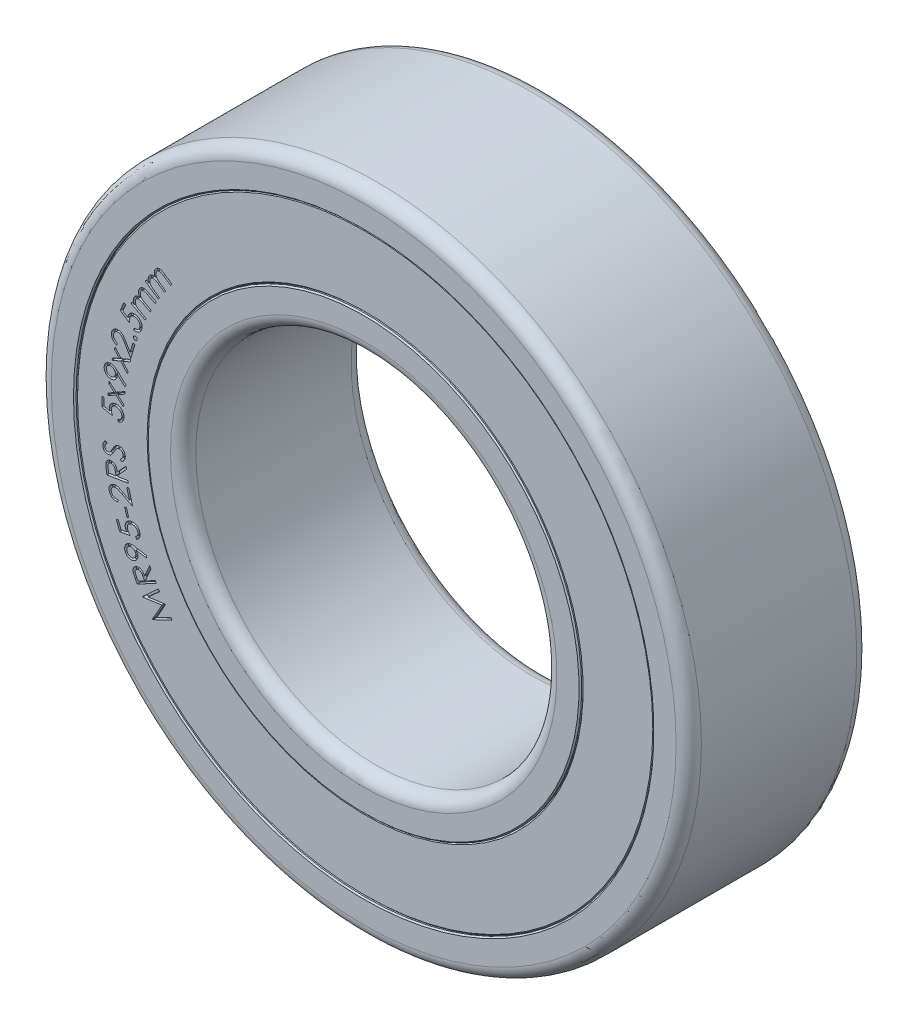
SolidWorks part; units mm, degrees
material "AISI 316 Annealed Stainless Steel Bar (SS)"
ref_plane "Front" through (0, 0, 0) normal (0, 0, 1) x (1, 0, 0)
ref_plane "Top" through (0, 0, 0) normal (0, 1, 0) x (1, 0, 0)
ref_plane "Right" through (0, 0, 0) normal (1, 0, 0) x (0, 0, -1)
sketch "LAYOUT R" plane through (0, 0, 0) normal (1, 0, 0) x (0, 0, -1)
  line L0 (-1.25, 2.5) -> (1.25, 2.5)
  line L1 (1.25, -4.5) -> (-1.25, -4.5) construction
  line L2 (1.25, -4.5) -> (1.25, 4.5) construction
  line L3 (1.25, 4.5) -> (-1.25, 4.5)
  line L4 (-1.25, -4.5) -> (-1.25, 4.5) construction
  line L5 (1.25, -4.5) -> (-1.25, 4.5) construction
  line L6 (1.25, 4.5) -> (-1.25, -4.5) construction
  line L7 (-1.25, 3) -> (1.25, 3)
  line L8 (-1.25, 4) -> (1.25, 4)
  line L11 (-17.5, 0) -> (17.5, 0) construction
  line L12 (-1.25, 4.5) -> (-1.25, 4)
  line L13 (1.25, 4.5) -> (1.25, 4)
  line L14 (-1.25, 4) -> (-1.25, 3)
  line L15 (1.25, 4) -> (1.25, 3)
  line L16 (-1.25, 3) -> (-1.25, 2.5)
  line L17 (1.25, 3) -> (1.25, 2.5)
  line L18 (-1.23, 4) -> (-1.23, 3)
  line L19 (1.23, 4) -> (1.23, 3)
  point P0 (0, 0)
  point P15 (0, 0)
  dimension "D1" = 2.5
  dimension "D2" = 9
  dimension "D3" = 2.5
  dimension "D6" = 0.02
  dimension "D7" = 0.02
  dimension "D4" = 3
  dimension "D5" = 4
sketch "Sketch R, INNER BODY" plane through (0, 0, 0) normal (1, 0, 0) x (0, 0, -1)
  line L0 (-1.25, 2.5) -> (1.25, 2.5) construction
  line L2 (-1.25, 3) -> (1.25, 3) construction
  line L4 (-1.25, 2.5) -> (1.25, 2.5)
  line L6 (-1.25, 3) -> (1.25, 3)
  line L8 (1.25, 3) -> (1.25, 2.5) construction
  line L9 (-1.25, 3) -> (-1.25, 2.5) construction
  line L10 (1.25, 3) -> (1.25, 2.5)
  line L11 (-1.25, 3) -> (-1.25, 2.5)
  line L12 (-17.5, 0) -> (17.5, 0) construction
  line L13 (-17.5, 0) -> (17.5, 0) construction
sketch "Sketch R, OUTER BODY" plane through (0, 0, 0) normal (1, 0, 0) x (0, 0, -1)
  line L2 (-1.25, 4) -> (1.25, 4) construction
  line L3 (1.25, 4.5) -> (-1.25, 4.5) construction
  line L6 (-1.25, 4) -> (1.25, 4)
  line L7 (1.25, 4.5) -> (-1.25, 4.5)
  line L8 (-17.5, 0) -> (17.5, 0) construction
  line L9 (-17.5, 0) -> (17.5, 0) construction
  line L10 (1.25, 4.5) -> (1.25, 4) construction
  line L11 (-1.25, 4.5) -> (-1.25, 4) construction
  line L12 (1.25, 4.5) -> (1.25, 4)
  line L13 (-1.25, 4.5) -> (-1.25, 4)
sketch "Sketch R, SEAL FACES" plane through (0, 0, 0) normal (1, 0, 0) x (0, 0, -1)
  line L0 (-17.5, 0) -> (17.5, 0) construction
  line L1 (-17.5, 0) -> (17.5, 0) construction
  line L3 (-1.25, 3) -> (1.25, 3) construction
  line L5 (-1.25, 4) -> (1.25, 4) construction
  line L7 (-1.23, 3) -> (1.23, 3)
  line L9 (-1.23, 4) -> (1.23, 4)
  line L10 (1.23, 4) -> (1.23, 3) construction
  line L11 (-1.23, 4) -> (-1.23, 3) construction
  line L12 (1.23, 4) -> (1.23, 3)
  line L13 (-1.23, 4) -> (-1.23, 3)
revolve "Revolve INNER BODY" add sketch "Sketch R, INNER BODY" angle 360 about L13
fillet "Fillet INNER BODY" radius 0.175 2 edges at (2.5, 0, 1.25) (2.5, 0, -1.25)
chamfer "Chamfer INNER BODY" distance 0.018 angle 45 2 edges at (3, 0, -1.25) (3, 0, 1.25)
revolve "Revolve OUTER BODY" add sketch "Sketch R, OUTER BODY" angle 360 about L9
fillet "Fillet OUTER BODY" radius 0.175 2 edges at (4.5, 0, -1.25) (4.5, 0, 1.25)
chamfer "Chamfer OUTER BODY" distance 0.018 angle 45 2 edges at (4, 0, 1.25) (4, 0, -1.25)
revolve "Revolve SEALS" add sketch "Sketch R, SEAL FACES" angle 360 about L1
chamfer "Chamfer SEALS" distance 0.018 angle 45 4 edges at (3, 0, -1.23) (4, 0, -1.23) (4, 0, 1.23) (3, 0, 1.23)
sketch "Sketch TEXT RADIUS 1 — MANUALLY ASSIGN TEXT AND FONT SIZE (FROM EQUATIONS)" plane through (0, 0, 1.23) normal (0, 0, 1) x (1, 0, 0)
  circle A0 centre (0, 0) radius 3.35 construction
  text T0 "MR95-2RS  5x9x2.5mm\r\n" font "Century Gothic" height 0.3
  dimension "D1" = 6.7
extrude "Cut-Extrude SEAL LABEL 1" cut sketch "Sketch TEXT RADIUS 1 — MANUALLY ASSIGN TEXT AND FONT SIZE (FROM EQUATIONS)" against normal blind 0.05
sketch "Sketch TEXT RADIUS 2 — MANUALLY ASSIGN TEXT AND FONT SIZE (FROM EQUATIONS)" plane through (0, 0, -1.23) normal (0, 0, -1) x (-1, 0, 0)
  circle A0 centre (0, 0) radius 3.35 construction
  text T0 "MR95-2RS  5x9x2.5mm" font "Century Gothic" height 0.3
  dimension "D1" = 6.7
extrude "Cut-Extrude SEAL LABEL 2" cut sketch "Sketch TEXT RADIUS 2 — MANUALLY ASSIGN TEXT AND FONT SIZE (FROM EQUATIONS)" against normal blind 0.05
equation "\"_i__BORE\"= 5"
equation "\"_i__OUTSIDE_DIAMETER\"= 9"
equation "\"_i__WIDTH\"= 2.5"
equation "\"_i_optional__TEXT_RADIUS_ADJUSTMENT\"= 0"
equation "\"_output__FONT_SIZE_mm\"= \"BODY_SPAN__SEAL__OF_RADIUS\" * \"param__FONT_SIZE_RATIO\"'MANUALLY ASSIGN TO FONT"
equation "\"BODY__HALF_WIDTH\"= \"_i__WIDTH\" / 2"
equation "\"BODY_SPAN___OF_DIAMETER\"= \"_i__OUTSIDE_DIAMETER\" - \"_i__BORE\""
equation "\"BODY_SPAN___OF_RADIUS\"= \"BODY_SPAN___OF_DIAMETER\" / 2"
equation "\"BODY_SPAN__BORE_AND_OD__OF RADIUS\"= ( \"BODY_SPAN___OF_RADIUS\" - \"BODY_SPAN__SEAL__OF_RADIUS\" ) / 2"
equation "\"BODY_SPAN__SEAL__OF_RADIUS\"= \"BODY_SPAN___OF_RADIUS\" * \"param__SEAL_PANEL_SPAN__RATIO_OF_BODY_RADIAN\""
equation "\"BORE__RADIUS\"= \"_i__BORE\" / 2"
equation "\"CORNER_RADII\"= \"_i__WIDTH\" * \"param__CORNER_RADII__ISO_MAX_RATIO_TO_WIDTH\""
equation "\"param__CORNER_RADII__ISO_MAX_RATIO_TO_WIDTH\"= 0.07'WHERE WIDTH IS LESS THAN DIAMETER"
equation "\"param__FONT_SIZE_RATIO\"= 0.3"
equation "\"param__SEAL_FACE_INSET__RATIO_OF_WIDTH\"= .01"
equation "\"param__SEAL_PANEL_SPAN__RATIO_OF_BODY_RADIAN\"= 0.5"
equation "\"param__SIDE_CHAMFERS__RATIO_TO_OD\"= 1 / 500"
equation "\"RING_INNER__OUTSIDE_RADIUS\"= \"BORE__RADIUS\" + \"BODY_SPAN__BORE_AND_OD__OF RADIUS\""
equation "\"RING_OUTER__OUTSIDE_RADIUS\"= ( \"_i__OUTSIDE_DIAMETER\" / 2 ) - \"BODY_SPAN__BORE_AND_OD__OF RADIUS\""
equation "\"SEAL_FACE_INSET\"= \"_i__WIDTH\" * \"param__SEAL_FACE_INSET__RATIO_OF_WIDTH\""
equation "\"SIDE_FACE_AND_SEAL_CHAMFERS\"= \"_i__OUTSIDE_DIAMETER\" * \"param__SIDE_CHAMFERS__RATIO_TO_OD\""
equation "\"TEXT_RADIUS\"= \"_i__BORE\" + ( \"BODY_SPAN___OF_DIAMETER\" / 2 ) - \"_output__FONT_SIZE_mm\" + \"_i_optional__TEXT_RADIUS_ADJUSTMENT\""
equation "\"D1@Chamfer INNER BODY\"=\"SIDE_FACE_AND_SEAL_CHAMFERS\""
equation "\"D1@Chamfer OUTER BODY\"=\"SIDE_FACE_AND_SEAL_CHAMFERS\""
equation "\"D1@Chamfer SEALS\"=\"SIDE_FACE_AND_SEAL_CHAMFERS\""
equation "\"D1@Fillet INNER BODY\"=\"CORNER_RADII\""
equation "\"D1@Fillet OUTER BODY\"=\"CORNER_RADII\""
equation "\"D1@LAYOUT R\"=\"_i__WIDTH\""
equation "\"D1@Sketch TEXT RADIUS 1 — MANUALLY ASSIGN TEXT AND FONT SIZE (FROM EQUATIONS)\" = \"TEXT_RADIUS\""
equation "\"D1@Sketch TEXT RADIUS 2 — MANUALLY ASSIGN TEXT AND FONT SIZE (FROM EQUATIONS)\" = \"TEXT_RADIUS\""
equation "\"D2@LAYOUT R\"=\"_i__OUTSIDE_DIAMETER\""
equation "\"D3@LAYOUT R\"=\"BORE__RADIUS\""
equation "\"D4@LAYOUT R\"=\"RING_INNER__OUTSIDE_RADIUS\""
equation "\"D5@LAYOUT R\"=\"RING_OUTER__OUTSIDE_RADIUS\""
